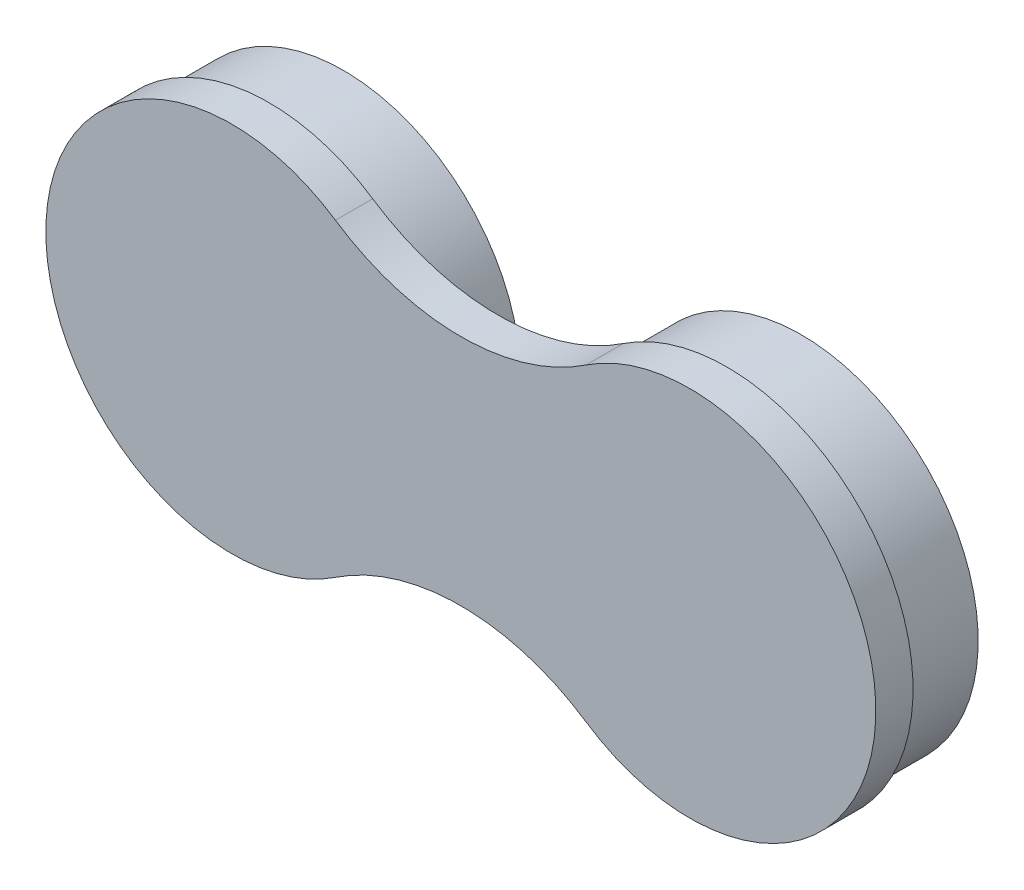
SolidWorks part; units mm, degrees
ref_plane "Front" through (0, 0, 0) normal (0, 0, 1) x (1, 0, 0)
ref_plane "Top" through (0, 0, 0) normal (0, 1, 0) x (1, 0, 0)
ref_plane "Right" through (0, 0, 0) normal (1, 0, 0) x (0, 0, -1)
sketch "Sketch1" plane through (0, 0, 0) normal (0, 0, 1) x (1, 0, 0)
  line L0 (0, 0) -> (0, 15) construction
  line L1 (0, 0) -> (-20.798, 0) construction
  circle A0 centre (-6.15, 0) radius 4.75
  circle A1 centre (6.15, 0) radius 4.75
  dimension "D1" = 9.5
  dimension "D2" = 12.3
extrude "Boss-Extrude1" add sketch "Sketch1" along normal blind 2
sketch "Sketch2" plane through (0, 0, 2) normal (0, 0, 1) x (1, 0, 0)
  circle A0 centre (6.15, 0) radius 4.75 construction
  circle A1 centre (-6.15, 0) radius 4.75 construction
  circle A2 centre (6.15, 0) radius 4.75
  circle A3 centre (-6.15, 0) radius 4.75
  circle A4 centre (-6.15, 0) radius 4.75
  circle A6 centre (-6.15, 0) radius 2.25
  circle A7 centre (6.15, 0) radius 2.25
  dimension "D1" = 4.5
extrude "Cut-Extrude1" cut sketch "Sketch2" against normal blind 2 contours A6
extrude "Cut-Extrude2" cut sketch "Sketch2<4>" against normal blind 2 contours A7
sketch "Sketch2<4>" plane through (0, 0, 2) normal (0, 0, 1) x (1, 0, 0) same geometry as "Sketch2"
sketch "Sketch4" plane through (0, 0, 2) normal (0, 0, 1) x (1, 0, 0)
  arc A0 (-3.3676, 4.1543) -> (-3.3677, -4.1544) centre (-6.15, 0) ccw
  arc A1 (3.3677, -4.1544) -> (3.3676, 4.1543) centre (6.15, 0) ccw
  arc A2 (-3.3676, 4.1543) -> (3.3676, 4.1543) centre (0, 9.1825) ccw
  arc A3 (-3.3677, -4.1544) -> (3.3677, -4.1544) centre (0, -9.1828) cw
  point P12 (-3.3676, 4.1543)
  dimension "D1" = 10
  dimension "D2" = 10
extrude "Boss-Extrude2" add sketch "Sketch4" along normal blind 1
